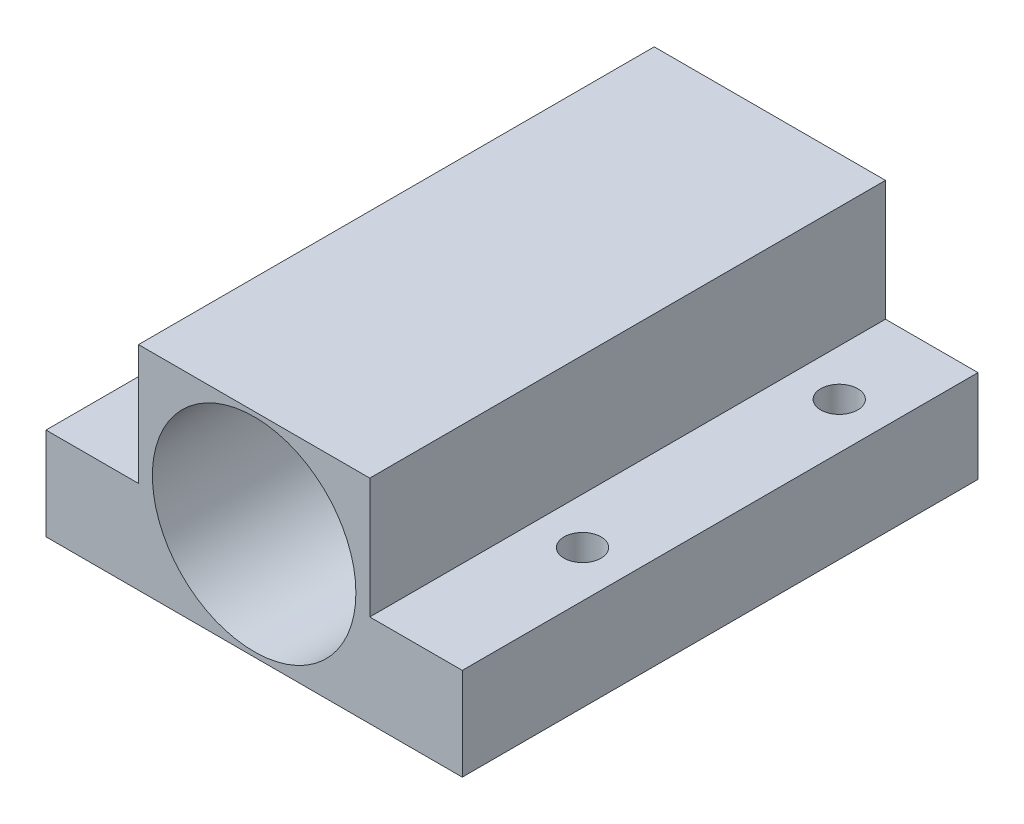
SolidWorks part; units mm, degrees
material "ABS"
ref_plane "Front Plane" through (0, 0, 0) normal (0, 0, 1) x (1, 0, 0)
ref_plane "Top Plane" through (0, 0, 0) normal (0, 1, 0) x (1, 0, 0)
ref_plane "Right Plane" through (0, 0, 0) normal (1, 0, 0) x (0, 0, -1)
sketch "Sketch1" plane through (0, 0, 0) normal (0, 0, 1) x (1, 0, 0)
  line L0 (-65.4098, -16.7) -> (184.5902, -16.7) construction
  line L1 (-12.5, 6.3) -> (12.5, 6.3)
  line L2 (-12.5, 6.3) -> (-12.5, -16.7)
  line L3 (-12.5, -16.7) -> (12.5, -16.7)
  line L4 (12.5, 6.3) -> (12.5, -16.7)
  line L5 (-12.5, 6.3) -> (12.5, -16.7) construction
  line L6 (-12.5, -16.7) -> (12.5, 6.3) construction
  line L7 (12.5, -16.7) -> (22.5, -16.7)
  line L8 (12.5, -16.7) -> (12.5, -6.7)
  line L9 (12.5, -6.7) -> (22.5, -6.7)
  line L10 (22.5, -16.7) -> (22.5, -6.7)
  line L11 (12.5, -16.7) -> (22.5, -6.7) construction
  line L12 (12.5, -6.7) -> (22.5, -16.7) construction
  line L13 (-12.5, -16.7) -> (-22.5, -16.7)
  line L14 (-12.5, -16.7) -> (-12.5, -6.7)
  line L15 (-12.5, -6.7) -> (-22.5, -6.7)
  line L16 (-22.5, -16.7) -> (-22.5, -6.7)
  line L17 (-12.5, -16.7) -> (-22.5, -6.7) construction
  line L18 (-12.5, -6.7) -> (-22.5, -16.7) construction
  circle A0 centre (0, -5.2) radius 4.1
  circle A1 centre (0, -5.2) radius 11
  point P8 (0, -5.2)
  point P14 (17.5, -11.7)
  point P16 (-17.5, -11.7)
  dimension "D4" = 8.2
  dimension "D5" = 22
  dimension "D11" = 11.5
  dimension "D2" = 0
  dimension "D3" = 25
  dimension "D6" = 10
  dimension "D7" = 10
  dimension "D8" = 10
  dimension "D9" = 10
  dimension "D10" = 12.5
  dimension "D12" = 11.5
  dimension "D13" = 5.2
extrude "Boss-Extrude1" add sketch "Sketch1" along normal up to surface (55.75 mm away) contours L4 L1 L2 L3 A1 | L16 L13 L2 L15 | L7 L10 L9 L4 region at (0, 5.9603, 0) region at (-17.5, -11.7, 0) region at (17.5, -11.7, 0)
sketch "Sketch2" plane through (0, -6.7, 0) normal (0, 1, 0) x (1, 0, 0)
  line L0 (-22.5, 0) -> (-12.5, -55.75)
  line L1 (-12.5, -55.75) -> (-22.5, -55.75)
  line L2 (-22.5, -55.75) -> (-12.5, 0)
  line L3 (12.5, 0) -> (22.5, -55.75)
  line L4 (22.5, -55.75) -> (22.5, 0)
  line L5 (22.5, 0) -> (12.5, -55.75)
  circle A0 centre (-17.5, -10) radius 2
  circle A1 centre (17.5, -10) radius 2
  circle A2 centre (17.5, -10) radius 2 construction
  circle A3 centre (-17.5, -10) radius 2 construction
  circle A4 centre (-17.5, -37.75) radius 2
  circle A5 centre (17.5, -37.75) radius 2
  circle A6 centre (17.5, -37.75) radius 2 construction
  circle A7 centre (-17.5, -37.75) radius 2 construction
  dimension "D1" = 4
  dimension "D2" = 4
extrude "Cut-Extrude1" cut sketch "Sketch2" against normal through all contours A0 | A4 | A1 | A5
